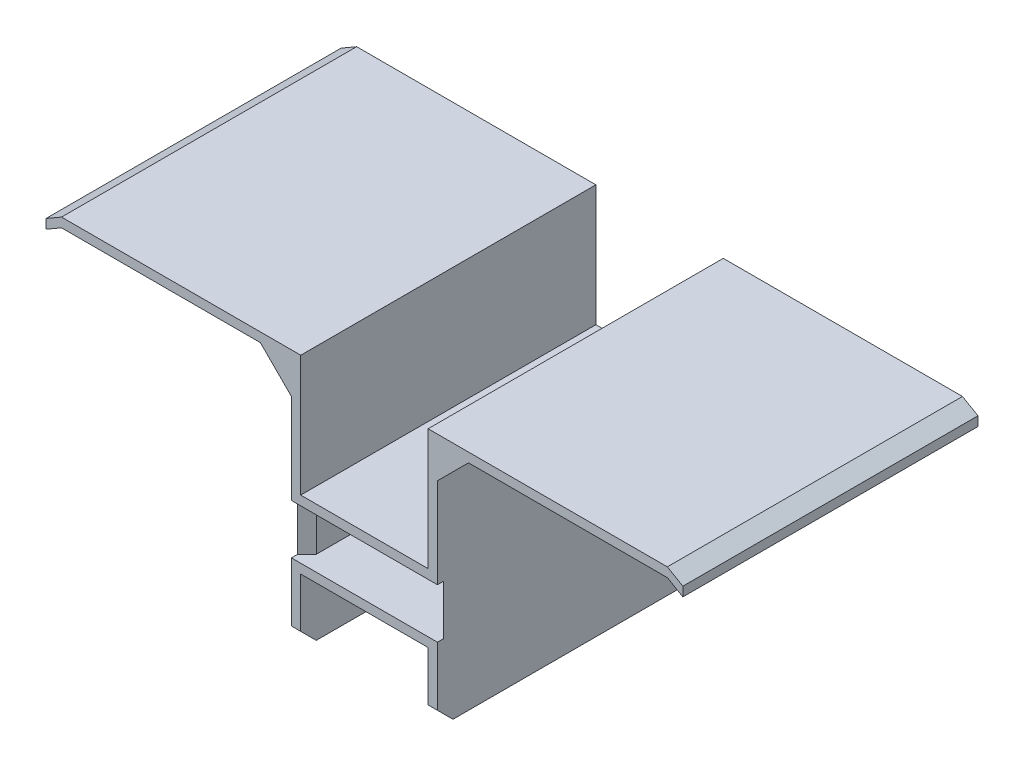
SolidWorks part; units mm, degrees
ref_plane "Front Plane" through (0, 0, 0) normal (0, 0, 1) x (1, 0, 0)
ref_plane "Top Plane" through (0, 0, 0) normal (0, 1, 0) x (1, 0, 0)
ref_plane "Right Plane" through (0, 0, 0) normal (1, 0, 0) x (0, 0, -1)
sketch "Sketch1" plane through (0, 0, 0) normal (0, 0, 1) x (1, 0, 0)
  line L0 (0, -55) -> (0, 55) construction
  line L1 (-23.5, 21) -> (23.5, 21)
  line L2 (-23.5, 21) -> (-23.5, -21)
  line L3 (-23.5, -21) -> (23.5, -21)
  line L4 (23.5, 21) -> (23.5, -21)
  line L5 (-23.5, 21) -> (23.5, -21) construction
  line L6 (-23.5, -21) -> (23.5, 21) construction
  point P0 (0, 0)
  dimension "D1" = 47
  dimension "D2" = 42
extrude "Boss-Extrude1" add sketch "Sketch1" along normal blind 95 contours L2 L1 L4 L3
shell "Shell1" thickness 3 removed face at (0, 21, 47.5) removed face at (0, 0, 95) removed face at (0, 0, 0)
sketch "Sketch2" plane through (-23.5, 0, 0) normal (-1, 0, 0) x (0, 0, 1)
  line L0 (0, -55) -> (0, 55) construction
  line L1 (95, 21) -> (0, 21)
  line L2 (95, 21) -> (95, 18)
  line L3 (95, 18) -> (0, 18)
  line L4 (0, 21) -> (0, 18)
  point P7 (10, 16.6102)
  dimension "D1" = 3
extrude "Boss-Extrude2" add sketch "Sketch2" along normal blind 74
mirror "Mirror1" about plane through (0, 0, 0) normal (1, 0, 0) of "Boss-Extrude2"
sketch "Sketch3" plane through (0, -21, 0) normal (0, -1, 0) x (1, 0, 0)
  line L0 (23.1, 0) -> (-23.1, 0) construction
  line L1 (-23.5, 95) -> (-20.5, 95)
  line L2 (-23.5, 95) -> (-23.5, 0)
  line L3 (-23.5, 0) -> (-20.5, 0)
  line L4 (-20.5, 95) -> (-20.5, 0)
  line L6 (23.5, 95) -> (20.5, 95)
  line L7 (23.5, 95) -> (23.5, 0)
  line L8 (23.5, 0) -> (20.5, 0)
  line L9 (20.5, 95) -> (20.5, 0)
  dimension "D1" = 3
  dimension "D2" = 3
extrude "Boss-Extrude3" add sketch "Sketch3" along normal blind 40
sketch "Sketch4" plane through (20.5, 0, 0) normal (-1, 0, 0) x (0, 0, 1)
  line L0 (0, -61) -> (0, -21) construction
  line L1 (0, -37) -> (95, -37)
  line L2 (0, -37) -> (0, -40)
  line L3 (0, -40) -> (95, -40)
  line L4 (95, -37) -> (95, -40)
  line L5 (95, -61) -> (95, -21) construction
  line L6 (95, -21) -> (0, -21) construction
  dimension "D1" = 16
  dimension "D2" = 3
extrude "Boss-Extrude4" add sketch "Sketch4" along normal up to surface (41 mm away) up to face at (-20.5, -41, 47.5)
chamfer "Chamfer2" distance 5 angle 45 4 edges at (-22, -61, 95) (22, -61, 95) (22, -61, 0) (-22, -61, 0)
chamfer "Chamfer3" distance 5 angle 45 4 edges at (20.5, -29, 95) (-20.5, -29, 95) (-20.5, -29, 0) (20.5, -29, 0)
sketch "Sketch5" plane through (0, 0, 0) normal (0, 0, -1) x (-1, 0, 0)
  line L0 (97.5, 18) -> (97.5, 21)
  line L1 (97.5, 18) -> (102.5, 15.1132)
  line L2 (97.5, 21) -> (102.5, 18.1132)
  line L3 (102.5, 15.1132) -> (102.5, 18.1132)
  line L4 (97.5, 18) -> (23.5, 18) construction
  dimension "D1" = 150
  dimension "D2" = 5
extrude "Boss-Extrude5" add sketch "Sketch5" against normal blind 95
mirror "Mirror2" about plane through (0, 0, 0) normal (1, 0, 0) of "Boss-Extrude5"
sketch "Sketch10" plane through (0, 18, 0) normal (0, -1, 0) x (1, 0, 0)
  line L0 (45.1, 0) -> (-45.1, 0) construction
  line L1 (-23.5, 95) -> (-33.5, 95)
  line L2 (-23.5, 95) -> (-23.5, 93)
  line L3 (-23.5, 93) -> (-33.5, 93)
  line L4 (-33.5, 95) -> (-33.5, 93)
  line L5 (-23.5, 0) -> (-33.5, 0)
  line L6 (-23.5, 0) -> (-23.5, 2)
  line L7 (-23.5, 2) -> (-33.5, 2)
  line L8 (-33.5, 0) -> (-33.5, 2)
  line L9 (-23.5, 0) -> (-23.5, 5) construction
  dimension "D1" = 10
  dimension "D2" = 2
  dimension "D3" = 10
  dimension "D4" = 2
extrude "Boss-Extrude7" add sketch "Sketch10" along normal blind 10
chamfer "Chamfer5" distance 10 angle 45 2 edges at (-33.5, 8, 94) (-33.5, 8, 1)
mirror "Mirror5" about plane through (0, 0, 0) normal (1, 0, 0) of "Boss-Extrude7", "Chamfer5"
